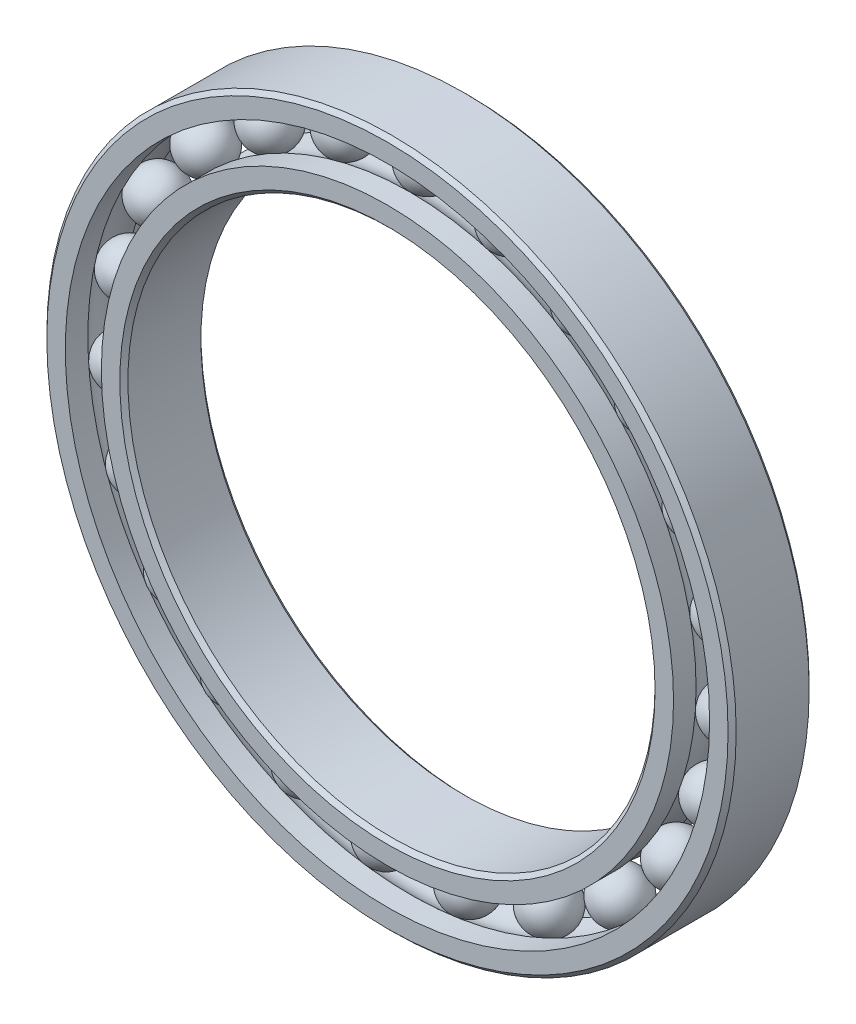
SolidWorks part; units mm, degrees
ref_plane "Front Plane" through (0, 0, 0) normal (0, 0, 1) x (1, 0, 0)
ref_plane "Top Plane" through (0, 0, 0) normal (0, 1, 0) x (1, 0, 0)
ref_plane "Right Plane" through (0, 0, 0) normal (1, 0, 0) x (0, 0, -1)
sketch "Sketch1" plane through (0, 0, 0) normal (0, 0, 1) x (1, 0, 0)
  circle A0 centre (0, 0) radius 42.5
  circle A1 centre (0, 0) radius 32.5
  dimension "OD" = 85
  dimension "ID" = 65
sketch "Sketch5" plane through (0, 0, 0) normal (1, 0, 0) x (0, 0, -1)
  line L0 (-5, 0) -> (5, 0) construction
  line L1 (0, 42.5) -> (0, -42.5) construction
  line L2 (4.5, 42.5) -> (-4.5, 42.5)
  line L3 (-4.5, 42.5) -> (-5, 42)
  line L4 (-5, 42) -> (-5, 39.7222)
  line L5 (-5, 39.7222) -> (-2.2222, 39.7222)
  line L6 (5, 39.7222) -> (2.2222, 39.7222)
  line L7 (5, 42) -> (5, 39.7222)
  line L8 (4.5, 42.5) -> (5, 42)
  line L9 (0, 42.5) -> (0, 37.5) construction
  line L10 (0, 37.5) -> (0, 32.5) construction
  line L11 (-3.1427, 37.5) -> (-5, 37.5) construction
  line L12 (3.8808, 35.3032) -> (4.2618, 35.3032) construction
  line L13 (-3.8808, 35.3032) -> (-4.2618, 35.3032) construction
  line L14 (-3.8808, 35.3032) -> (-3.8808, 39.6968) construction
  line L15 (-3.8808, 39.6968) -> (-4.2618, 39.6968) construction
  line L16 (-4.2618, 35.3032) -> (-4.2618, 39.6968) construction
  line L17 (-3.8808, 35.3032) -> (-4.2618, 39.6968) construction
  line L18 (-3.8808, 39.6968) -> (-4.2618, 35.3032) construction
  line L19 (4.2618, 35.3032) -> (4.2618, 39.6968) construction
  line L20 (3.8808, 39.6968) -> (4.2618, 39.6968) construction
  line L21 (3.8808, 35.3032) -> (3.8808, 39.6968) construction
  line L22 (0, 42.5) -> (0, -42.5) construction
  arc A0 (-2.2222, 39.7222) -> (2.2222, 39.7222) centre (0, 37.5) cw
  circle A1 centre (0, 37.5) radius 3.1427 construction
  point P14 (0, 32.5)
  point P15 (-4.0713, 37.5)
  dimension "Width" = 10
  dimension "D1" = 45
  dimension "D2" = 0.5
  dimension "D3" = 4.4444
  dimension "D4" = 2.2222
  dimension "D5" = 0.381
  dimension "D6" = 0.0254
  dimension "D7" = 10
revolve "Revolve1" add sketch "Sketch5" angle 360 about L0
sketch "Sketch3" plane through (0, 0, 0) normal (1, 0, 0) x (0, 0, -1)
  line L0 (-5, 35.2778) -> (-2.2222, 35.2778)
  line L1 (0, 42.5) -> (0, -42.5) construction
  line L2 (-5, 42) -> (-5, 39.7222) construction
  line L3 (-5, 35.2778) -> (-5, 33)
  line L4 (-4.5, 42.5) -> (-5, 42) construction
  line L5 (-5, 33) -> (-4.5, 32.5)
  line L6 (-4.5, 32.5) -> (4.5, 32.5)
  line L7 (4.5, 42.5) -> (4.5, -42.5) construction
  line L8 (4.5, 32.5) -> (5, 33)
  line L9 (5, -42) -> (5, 42) construction
  line L10 (5, 33) -> (5, 35.2778)
  line L11 (5, 35.2778) -> (2.2222, 35.2778)
  line L13 (4.5, 42.5) -> (5, 42) construction
  arc A0 (2.2222, 39.7222) -> (-2.2222, 39.7222) centre (0, 37.5) ccw construction
  arc A1 (2.2222, 35.2778) -> (-2.2222, 35.2778) centre (0, 37.5) cw
revolve "Revolve3" add sketch "Sketch3" angle 360 about L0
sketch "Sketch4" plane through (0, 0, 0) normal (1, 0, 0) x (0, 0, -1)
  line L0 (-3.1427, 37.5) -> (3.1427, 37.5)
  arc A2 (-3.1427, 37.5) -> (3.1427, 37.5) centre (0, 37.5) cw
  arc A3 (2.2222, 39.7222) -> (-2.2222, 39.7222) centre (0, 37.5) ccw construction
revolve "Revolve4" add sketch "Sketch4" angle 360 about L0
pattern_circular "CirPattern1" count 23 every 15.652 of bodies 104
ref_axis "Center Axis 1" through (0, 0, -4.5) along (0, 0, 1)
equation "\"D2@Sketch5\" = \"Width@Sketch5\" * .05"
equation "\"D3@Sketch5\" = \"Width@Sketch5\" / 2.25"
equation "\"D4@Sketch5\"=((\"OD@Sketch1\"-\"ID@Sketch1\")/2)/4.5"
equation "\"D2@CirPattern1\" = 360/\"Balls@CirPattern1\""
